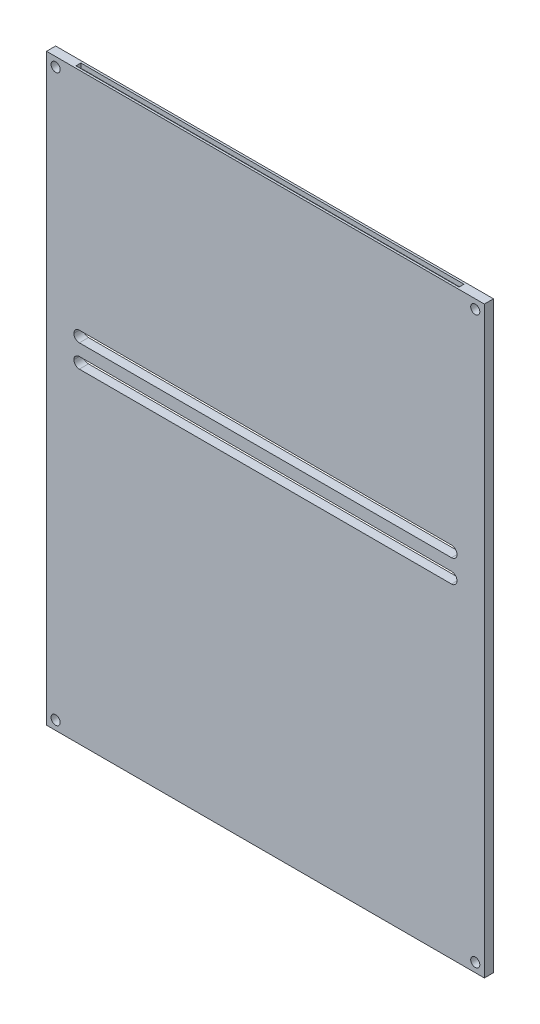
SolidWorks part; units mm, degrees
ref_plane "Front Plane" through (0, 0, 0) normal (0, 0, 1) x (1, 0, 0)
ref_plane "Top Plane" through (0, 0, 0) normal (0, 1, 0) x (1, 0, 0)
ref_plane "Right Plane" through (0, 0, 0) normal (1, 0, 0) x (0, 0, -1)
sketch "Sketch1" plane through (0, 0, 0) normal (0, 0, 1) x (1, 0, 0)
  line L0 (0, 160.065) -> (0, -160.065) construction
  line L1 (-120.075, 0) -> (120.075, 0) construction
  line L2 (-120.075, 160.065) -> (120.075, 160.065)
  line L3 (120.075, 160.065) -> (120.075, -160.065)
  line L4 (120.075, -160.065) -> (-120.075, -160.065)
  line L5 (-120.075, -160.065) -> (-120.075, 160.065)
  circle A0 centre (-115.075, 155.065) radius 2.5
  circle A1 centre (115.075, 155.065) radius 2.5
  circle A2 centre (-115.075, -155.065) radius 2.5
  circle A3 centre (115.075, -155.065) radius 2.5
  dimension "D3" = 5
  dimension "D4" = 5
  dimension "D5" = 5
  dimension "D6" = 5
  dimension "D7" = 5
  dimension "D8" = 5
  dimension "D9" = 5
  dimension "D10" = 5
  dimension "D11" = 5
  dimension "D12" = 5
  dimension "D13" = 5
  dimension "D14" = 5
  dimension "D1" = 240.15
  dimension "D2" = 320.13
extrude "Boss-Extrude1" add sketch "Sketch1" along normal blind 5
sketch "Sketch2" plane through (0, 160.065, 0) normal (0, 1, 0) x (1, 0, 0)
  line L1 (-120.075, -5) -> (-120.075, 0) construction
  line L2 (120.075, -5) -> (120.075, 0) construction
  line L3 (-120.075, -2.5) -> (120.075, -2.5) construction
  circle A0 centre (-105.075, -2.5) radius 1
  circle A1 centre (105.075, -2.5) radius 1
  dimension "D1" = 2
  dimension "D2" = 2
  dimension "D5" = 15
  dimension "D6" = 15
sketch "Sketch3" plane through (0, 0, 5) normal (0, 0, 1) x (1, 0, 0)
  line L0 (-120.075, 33.575) -> (120.075, 33.575) construction
  line L1 (-120.075, 160.065) -> (-120.075, -160.065) construction
  line L2 (120.075, -160.065) -> (120.075, 160.065) construction
  line L3 (120.075, 160.065) -> (-120.075, 160.065) construction
  line L4 (-120.075, 27.325) -> (120.075, 27.325) construction
  line L5 (105.075, 30.575) -> (-105.075, 30.575)
  line L6 (105.075, 30.575) -> (105.075, 36.575)
  line L7 (105.075, 36.575) -> (-105.075, 36.575)
  line L8 (-105.075, 30.575) -> (-105.075, 36.575)
  line L9 (105.075, 30.575) -> (-105.075, 36.575) construction
  line L10 (105.075, 36.575) -> (-105.075, 30.575) construction
  line L11 (105.075, 24.075) -> (-105.075, 24.075)
  line L12 (105.075, 24.075) -> (105.075, 18.075)
  line L13 (-105.075, 24.075) -> (-105.075, 18.075)
  line L14 (105.075, 18.075) -> (-105.075, 18.075)
  point P8 (0, 33.575)
  dimension "D1" = 126.49
  dimension "D2" = 15
  dimension "D3" = 6
  dimension "D4" = 6.25
extrude "Cut-Extrude2" cut sketch "Sketch3" against normal up to next
fillet "Fillet1" radius 3 4 edges at (105.075, 30.575, 2.5) (105.075, 36.575, 2.5) (-105.075, 30.575, 2.5) (-105.075, 36.575, 2.5)
sketch "Sketch4" plane through (0, 160.065, 0) normal (0, 1, 0) x (1, 0, 0)
  line L0 (-120.075, -2.5) -> (120.075, -2.5) construction
  line L2 (105.075, -3.85) -> (-105.075, -3.85)
  line L3 (105.075, -3.85) -> (105.075, -1.15)
  line L4 (105.075, -1.15) -> (-105.075, -1.15)
  line L5 (-105.075, -3.85) -> (-105.075, -1.15)
  line L6 (105.075, -3.85) -> (-105.075, -1.15) construction
  line L7 (105.075, -1.15) -> (-105.075, -3.85) construction
  point P4 (0, -2.5)
  dimension "D1" = 2.7
extrude "Cut-Extrude3" cut sketch "Sketch4" against normal blind 2.5
ref_plane "Plane1" through (0, 27.325, 0) normal (0, 1, 0) x (1, 0, 0)
fillet "Fillet2" radius 3 4 edges at (-105.075, 18.075, 2.5) (-105.075, 24.075, 2.5) (105.075, 18.075, 2.5) (105.075, 24.075, 2.5)
